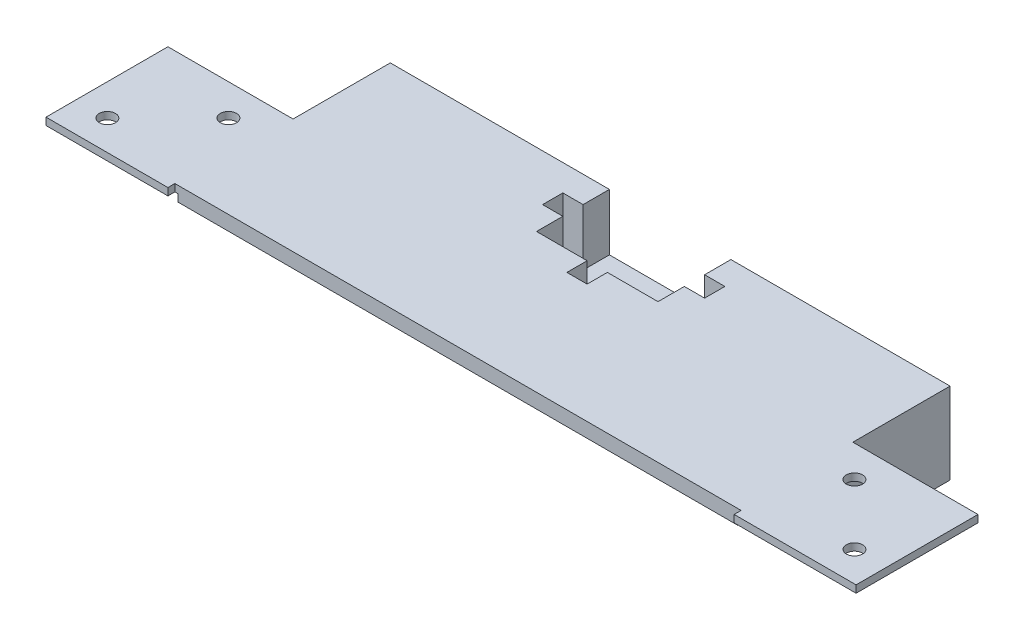
SolidWorks part; units mm, degrees
ref_plane "Alzado" through (0, 0, 0) normal (0, 0, 1) x (1, 0, 0)
ref_plane "Planta" through (0, 0, 0) normal (0, 1, 0) x (1, 0, 0)
ref_plane "Vista lateral" through (0, 0, 0) normal (1, 0, 0) x (0, 0, -1)
sketch "Croquis1" plane through (0, 0, 0) normal (0, 1, 0) x (1, 0, 0)
  line L0 (0, 16.8548) -> (0, -58.7896) construction
  line L1 (-69.5, -36.2916) -> (-69.5, -34.5716) construction
  line L2 (-100, -36.2916) -> (-69.5, -36.2916) construction
  line L3 (-100, -5.7916) -> (-100, -36.2916) construction
  line L4 (-69.5, -5.7916) -> (-100, -5.7916) construction
  line L5 (-69.5, -34.5716) -> (-69.5, -5.7916) construction
  line L17 (-69.5, -9.7916) -> (69.5, -9.7916) construction
  line L18 (69.5, -34.5716) -> (69.5, -5.7916) construction
  line L19 (69.5, -5.7916) -> (100, -5.7916) construction
  line L20 (100, -5.7916) -> (100, -36.2916) construction
  line L21 (100, -36.2916) -> (69.5, -36.2916) construction
  line L22 (69.5, -36.2916) -> (69.5, -34.5716) construction
  line L23 (69.5, -34.5716) -> (-69.5, -34.5716) construction
  circle A0 centre (-77.2782, -13.5698) radius 2 construction
  circle A1 centre (-92.2218, -28.5135) radius 2 construction
  circle A2 centre (-56.5, -26.2016) radius 2 construction
  circle A11 centre (56.5, -26.2016) radius 2 construction
  circle A12 centre (92.2218, -28.5135) radius 2 construction
  circle A13 centre (77.2782, -13.5698) radius 2 construction
  point P23 (0, -34.5716)
  point P28 (0, -9.7916)
sketch "Croquis4" plane through (0, 0, 0) normal (0, 1, 0) x (1, 0, 0)
  line L0 (69.5, -34.5716) -> (-69.5, -34.5716) construction
  line L1 (100, -36.2916) -> (69.5, -36.2916) construction
  line L2 (100, -5.7916) -> (100, -36.2916) construction
  line L3 (69.5, -5.7916) -> (100, -5.7916) construction
  line L5 (-69.5, -9.7916) -> (69.5, -9.7916) construction
  line L6 (0, 16.8548) -> (0, -58.7896) construction
  line L7 (69.5, -34.5716) -> (0, -34.5716) construction
  line L8 (100, -36.2916) -> (69.5, -36.2916) construction
  line L9 (100, -5.7916) -> (100, -36.2916) construction
  line L10 (69.5, -5.7916) -> (100, -5.7916) construction
  line L12 (0, -9.7916) -> (69.5, -9.7916) construction
  line L13 (0, 16.8548) -> (0, -58.7896) construction
  line L15 (69.5, -36.2916) -> (69.5, -34.5716) construction
  line L16 (69.5, -36.2916) -> (69.5, -34.5716) construction
  line L17 (100, -35.8916) -> (69.9, -35.8916)
  line L18 (69.9, -35.8916) -> (69.9, -34.1716)
  line L19 (69.9, -34.1716) -> (0, -34.1716)
  line L20 (100, -35.8916) -> (100, -5.7916)
  line L22 (100, -5.7916) -> (-100, -5.7916)
  line L23 (-69.9, -34.1716) -> (0, -34.1716)
  line L24 (-69.9, -35.8916) -> (-69.9, -34.1716)
  line L25 (-100, -35.8916) -> (-69.9, -35.8916)
  line L26 (-100, -35.8916) -> (-100, -5.7916)
  point P21 (0, -5.7916)
  dimension "D1" = 0.4
extrude "Saliente-Extruir1" add sketch "Croquis4" along normal blind 1.8
sketch "Croquis5" plane through (0, 1.8, 0) normal (0, 1, 0) x (1, 0, 0)
  line L0 (69.5, -34.5716) -> (-69.5, -34.5716) construction
  line L1 (69.5, -34.5716) -> (69.5, -5.7916) construction
  line L2 (-69.5, -9.7916) -> (69.5, -9.7916) construction
  line L3 (0, 16.8548) -> (0, -58.7896) construction
  line L4 (69.5, -34.5716) -> (0, -34.5716) construction
  line L5 (69.5, -34.5716) -> (69.5, -9.7916) construction
  line L6 (0, -9.7916) -> (69.5, -9.7916) construction
  line L7 (0, 16.8548) -> (0, -58.7896) construction
  line L11 (-69.1, -34.1716) -> (69.1, -34.1716)
  line L17 (-69.9, -34.1716) -> (69.9, -34.1716) construction
  line L18 (69.1, -34.1716) -> (69.1, -9.7916)
  line L19 (69.1, -34.5716) -> (69.1, -9.7916) construction
  line L20 (69.1, -9.7916) -> (69.1, -5.7916)
  line L21 (100, -5.7916) -> (-100, -5.7916) construction
  line L22 (69.1, -5.7916) -> (-69.1, -5.7916)
  line L23 (-69.1, -34.1716) -> (-69.1, -9.7916)
  line L24 (-69.1, -9.7916) -> (-69.1, -5.7916)
  point P20 (0, -10.2916)
  point P21 (0, -34.1716)
  point P23 (0, -5.7916)
  dimension "D1" = 0.4
extrude "Saliente-Extruir2" add sketch "Croquis5" against normal blind 1.8 from surface starting at face at (0, 0, 27.9366)
sketch "Croquis6" plane through (0, 1.8, 0) normal (0, 1, 0) x (1, 0, 0)
  line L0 (-69.5, -9.7916) -> (69.5, -9.7916) construction
  line L1 (0, -9.7916) -> (69.5, -9.7916) construction
  line L2 (0, 16.8548) -> (0, -58.7896) construction
  line L3 (0, 16.8548) -> (0, -58.7896) construction
  line L4 (69.5, -34.5716) -> (69.5, -5.7916) construction
  line L5 (69.5, -9.7916) -> (69.5, -5.7916) construction
  line L14 (-69.1, -9.1916) -> (69.1, -9.1916)
  line L15 (69.1, -9.1916) -> (69.1, -5.7916)
  line L16 (69.1, -9.7916) -> (69.1, -5.7916) construction
  line L17 (0, -9.1916) -> (69.5, -9.1916) construction
  line L18 (69.1, -5.7916) -> (-69.1, -5.7916)
  line L19 (100, -5.7916) -> (-100, -5.7916) construction
  line L20 (-69.1, -9.1916) -> (-69.1, -5.7916)
  point P17 (0, -5.7916)
  dimension "D1" = 0.6
  dimension "D2" = 0.4
extrude "Saliente-Extruir3" add sketch "Croquis6" against normal blind 16.5 from surface starting at face at (0, -1.8, 19.9816)
sketch "Croquis7" plane through (0, 0, 5.7916) normal (0, 0, -1) x (-1, 0, 0)
  line L0 (0, 22.365) -> (0, -38.5622) construction
  line L1 (0, 1.8) -> (75, 1.8)
  line L2 (-100, 1.8) -> (100, 1.8) construction
  line L3 (75, 1.8) -> (75, -18.3)
  line L4 (-69.1, -18.3) -> (69.1, -18.3) construction
  line L5 (75, -18.3) -> (0, -18.3)
  dimension "D1" = 75
sketch "Croquis8" plane through (0, 0, 5.7916) normal (0, 0, -1) x (-1, 0, 0)
  line L0 (0, 22.365) -> (0, -38.5622) construction
  line L1 (0, 22.365) -> (0, -38.5622) construction
  line L2 (-69.1, 1.8) -> (69.1, 1.8)
  line L3 (0, 1.8) -> (75, 1.8) construction
  line L4 (69.1, 1.8) -> (69.1, -18.3)
  line L5 (69.1, -18.3) -> (-69.1, -18.3)
  line L6 (-69.1, 1.8) -> (-69.1, -18.3)
  point P12 (0, 1.8)
  point P13 (0, -18.3)
extrude "Saliente-Extruir4" add sketch "Croquis8" along normal blind 24
sketch "Croquis9" plane through (0, 1.8, 0) normal (0, 1, 0) x (1, 0, 0)
  line L0 (0, 16.8548) -> (0, -58.7896) construction
  line L1 (0, 33.1742) -> (0, -58.7896) construction
  line L2 (15, 18.2084) -> (-15, 18.2084)
  line L3 (-69.1, 18.2084) -> (69.1, 18.2084) construction
  line L4 (-15, 18.2084) -> (-15, 0.2084)
  line L5 (-15, 0.2084) -> (15, 0.2084)
  line L6 (15, 18.2084) -> (15, 0.2084)
  point P10 (0, 0.2084)
  point P11 (0, 18.2084)
  dimension "D1" = 18
  dimension "D2" = 15
extrude "Cortar-Extruir1" cut sketch "Croquis9" against normal blind 14
sketch "Croquis10" plane through (0, -12.2, 0) normal (0, 1, 0) x (1, 0, 0)
  line L0 (0, 16.8548) -> (0, -58.7896) construction
  line L1 (0, 22.5663) -> (0, -58.7896) construction
  line L2 (15, 18.2084) -> (-15, 18.2084) construction
  line L3 (15, 18.2084) -> (-15, 18.2084) construction
  circle A0 centre (-4.75, 10.2084) radius 1
  circle A1 centre (4.75, 10.2084) radius 1
  dimension "D1" = 2
  dimension "D2" = 4.75
  dimension "D3" = 8
sketch "Croquis11" plane through (0, 1.8, 0) normal (0, 1, 0) x (1, 0, 0)
  circle A0 centre (92.2218, -28.5135) radius 2 construction
  circle A1 centre (77.2782, -13.5698) radius 2 construction
  circle A2 centre (-77.2782, -13.5698) radius 2 construction
  circle A3 centre (-92.2218, -28.5135) radius 2 construction
  circle A4 centre (92.2218, -28.5135) radius 2
  circle A5 centre (77.2782, -13.5698) radius 2
  circle A6 centre (-77.2782, -13.5698) radius 2
  circle A7 centre (-92.2218, -28.5135) radius 2
extrude "Cortar-Extruir2" cut sketch "Croquis11" against normal through all
sketch "Croquis12" plane through (0, -18.3, 0) normal (0, 1, 0) x (1, 0, 0)
  line L0 (-17.044, 0.2084) -> (17.044, 0.2084) construction
  text T0 "NUT BOT" font "Century Gothic" height 6
  point P7 (0, 0.2084)
extrude "Cortar-Extruir4" cut sketch "Croquis12" along normal blind 1
sketch "Croquis14" plane through (0, 1.8, 0) normal (0, 1, 0) x (1, 0, 0)
  line L0 (15, 0.2084) -> (15, 18.2084) construction
  line L1 (-15, 18.2084) -> (-15, 0.2084) construction
  line L2 (15, 0.2084) -> (15, 18.2084) construction
  line L3 (-15, 18.2084) -> (-15, 0.2084) construction
  line L4 (-18.7981, 9.2084) -> (18.7981, 9.2084) construction
  line L5 (0, 20.6624) -> (0, -12.0045) construction
  line L7 (20, 6.7084) -> (15, 6.7084)
  line L8 (-20, 11.7084) -> (-15, 11.7084)
  line L9 (-20, 11.7084) -> (-20, 6.7084)
  line L10 (-20, 6.7084) -> (-15, 6.7084)
  line L11 (-15, 11.7084) -> (-15, 6.7084)
  line L12 (-20, 11.7084) -> (-15, 6.7084) construction
  line L13 (-20, 6.7084) -> (-15, 11.7084) construction
  line L14 (15, 11.7084) -> (15, 6.7084)
  line L19 (-15, 0.2084) -> (15, 0.2084) construction
  line L20 (2.5, -4.7916) -> (-2.5, -4.7916)
  line L21 (2.5, -4.7916) -> (2.5, 0.2084)
  line L22 (2.5, 0.2084) -> (-2.5, 0.2084)
  line L23 (-2.5, -4.7916) -> (-2.5, 0.2084)
  line L24 (2.5, -4.7916) -> (-2.5, 0.2084) construction
  line L25 (2.5, 0.2084) -> (-2.5, -4.7916) construction
  line L26 (20, 11.7084) -> (15, 11.7084)
  line L27 (20, 11.7084) -> (20, 6.7084)
  point P6 (-15, 9.2084)
  point P13 (-17.5, 9.2084)
  point P22 (17.5, 9.2084)
  point P23 (0, -2.2916)
  dimension "D1" = 5
  dimension "D2" = 5
  dimension "D3" = 5
  dimension "D4" = 5
extrude "Cortar-Extruir5" cut sketch "Croquis14" against normal up to surface (14 mm away) up to face at (0, -12.2, -9.2084)
